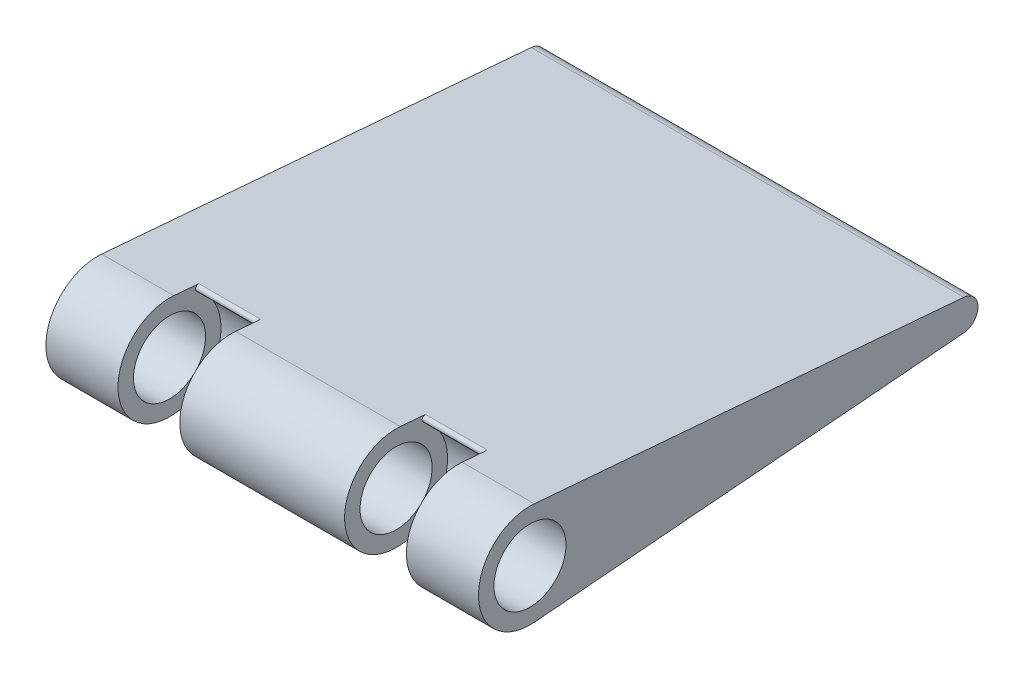
SolidWorks part; units mm, degrees
ref_plane "Front Plane" through (0, 0, 0) normal (0, 0, 1) x (1, 0, 0)
ref_plane "Top Plane" through (0, 0, 0) normal (0, 1, 0) x (1, 0, 0)
ref_plane "Right Plane" through (0, 0, 0) normal (1, 0, 0) x (0, 0, -1)
sketch "Sketch1" plane through (0, 0, 0) normal (1, 0, 0) x (0, 0, -1)
  line L0 (0.4167, 4.9826) -> (42.125, 1.4948)
  line L1 (0.4167, -4.9826) -> (42.125, -1.4948)
  circle A0 centre (0, 0) radius 5
  circle A1 centre (0, 0) radius 3.5
  circle A2 centre (42, 0) radius 1.5
  dimension "D1" = 10
  dimension "D2" = 7
  dimension "D3" = 3
  dimension "D4" = 42
extrude "Boss-Extrude1" add sketch "Sketch1" along normal mid plane 42 contours A2 L0 A0 L1 | A0 A1 | A2 region at (0, 0, -19.429) region at (0, 3.2893, -3.5758) region at (0, 0, -42)
extrude "Cut-Extrude1" cut sketch "Sketch1<3>" along normal blind 6 from offset 8 contours A0 A1 region at (0, 3.2893, -3.5758)
sketch "Sketch1<3>" plane through (0, 0, 0) normal (1, 0, 0) x (0, 0, -1) same geometry as "Sketch1"
extrude "Cut-Extrude2" cut sketch "Sketch1<4>" against normal blind 6 from offset 8 contours A0 A1 region at (0, 3.2893, -3.5758) offset against normal yes
sketch "Sketch1<4>" plane through (0, 0, 0) normal (1, 0, 0) x (0, 0, -1) same geometry as "Sketch1"
fillet "Fillet1" radius 0.3 4 edges at (-11, -4.9826, -0.4167) (-11, 4.9826, -0.4167) (11, -4.9826, -0.4167) (11, 4.9826, -0.4167)
